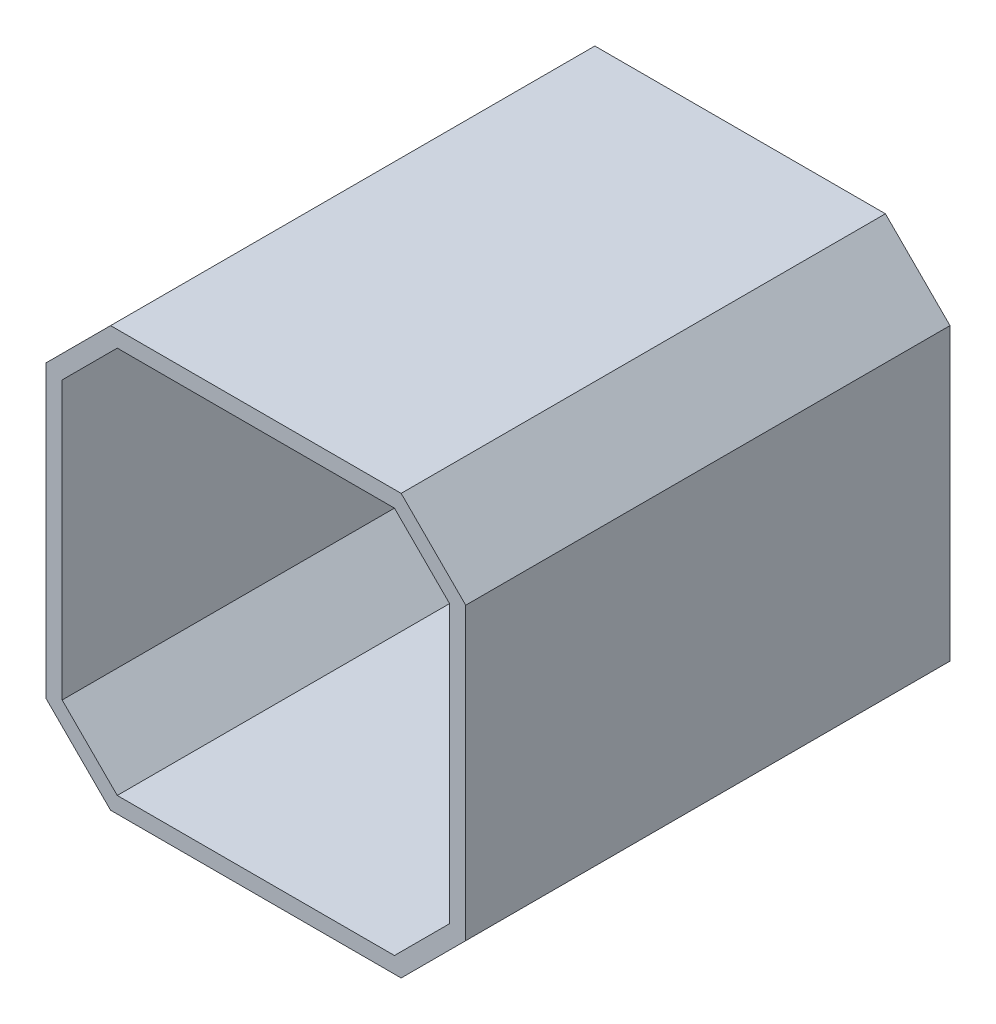
SolidWorks part; units mm, degrees
ref_plane "Front Plane" through (0, 0, 0) normal (0, 0, 1) x (1, 0, 0)
ref_plane "Top Plane" through (0, 0, 0) normal (0, 1, 0) x (1, 0, 0)
ref_plane "Right Plane" through (0, 0, 0) normal (1, 0, 0) x (0, 0, -1)
sketch "Sketch1" plane through (0, 0, 0) normal (0, 0, 1) x (1, 0, 0)
  line L0 (-32.5, 22.5) -> (-22.5, 32.5)
  line L1 (-22.5, -32.5) -> (22.5, -32.5)
  line L2 (-32.5, -22.5) -> (-32.5, 22.5)
  line L3 (-22.5, 32.5) -> (22.5, 32.5)
  line L4 (32.5, -22.5) -> (32.5, 22.5)
  line L5 (-27.5, -27.5) -> (27.5, 27.5) construction
  line L6 (-32.5, 32.5) -> (27.5, -27.5) construction
  line L7 (22.5, 32.5) -> (32.5, 22.5)
  line L8 (32.5, -22.5) -> (22.5, -32.5)
  line L9 (-22.5, -32.5) -> (-32.5, -22.5)
  line L10 (-30, 21.4645) -> (-21.4645, 30)
  line L11 (-21.4645, 30) -> (21.4645, 30)
  line L12 (21.4645, 30) -> (30, 21.4645)
  line L13 (30, -21.4645) -> (30, 21.4645)
  line L14 (30, -21.4645) -> (21.4645, -30)
  line L15 (-21.4645, -30) -> (21.4645, -30)
  line L16 (-21.4645, -30) -> (-30, -21.4645)
  line L17 (-30, -21.4645) -> (-30, 21.4645)
  point P0 (0, 0)
  point P17 (0, 0)
  dimension "D1" = 2.5
  dimension "D3" = 4
extrude "Boss-Extrude1" add sketch "Sketch1" along normal blind 75
sketch "Sketch2" plane through (0, 0, 0) normal (0, 0, 1) x (1, 0, 0)
  line L0 (30, 21.4645) -> (21.4645, 30)
  line L1 (21.4645, 30) -> (-21.4645, 30)
  line L2 (-21.4645, 30) -> (-30, 21.4645)
  line L3 (-30, 21.4645) -> (-30, -21.4645)
  line L4 (-30, -21.4645) -> (-21.4645, -30)
  line L5 (-21.4645, -30) -> (21.4645, -30)
  line L6 (21.4645, -30) -> (30, -21.4645)
  line L7 (30, -21.4645) -> (30, 21.4645)
  circle A0 centre (0, 0) radius 5
  dimension "D1" = 10
extrude "Boss-Extrude2" add sketch "Sketch2" along normal blind 2.5
